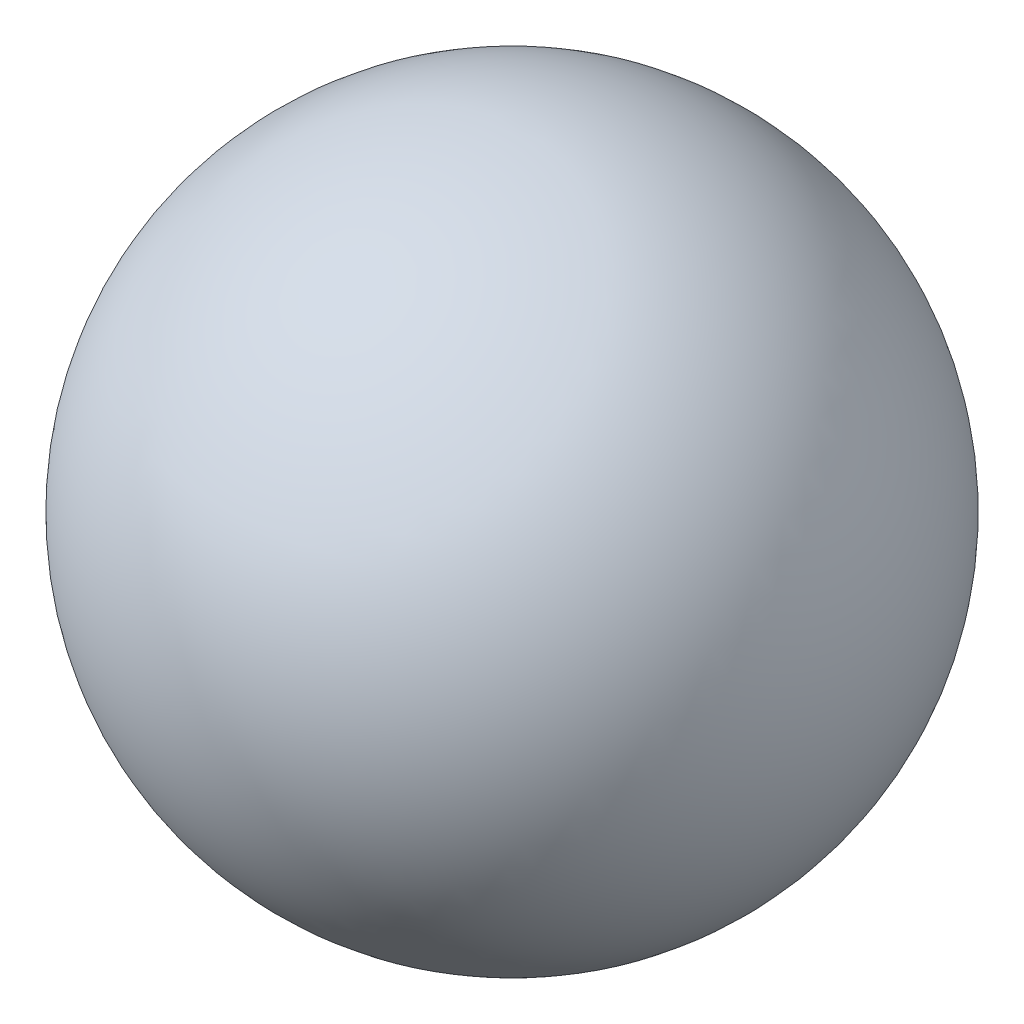
SolidWorks part; units mm, degrees
material "ｼﾘｺﾝ ｺﾞﾑ"
ref_plane "正面" through (0, 0, 0) normal (0, 0, 1) x (1, 0, 0)
ref_plane "平面" through (0, 0, 0) normal (0, 1, 0) x (1, 0, 0)
ref_plane "右側面" through (0, 0, 0) normal (1, 0, 0) x (0, 0, -1)
sketch "ｽｹｯﾁ1" plane through (0, 0, 0) normal (0, 0, 1) x (1, 0, 0)
  line L0 (0, -137.5) -> (0, 137.5) construction
  line L1 (0, 120) -> (0, -120)
  arc A0 (0, 120) -> (0, -120) centre (0, 0) cw
  dimension "D1" = 240
revolve "回転1" add sketch "ｽｹｯﾁ1" angle 360 about L1 region at (50.9296, 0, 0)
